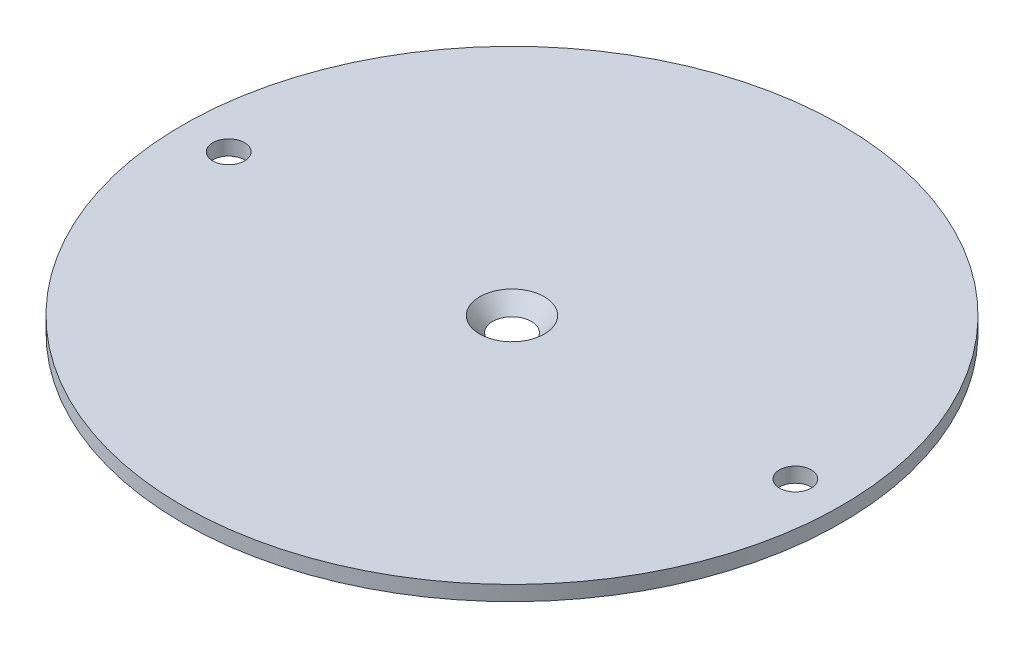
SolidWorks part; units mm, degrees
material "6061 Alloy"
ref_plane "Front Plane" through (0, 0, 0) normal (0, 0, 1) x (1, 0, 0)
ref_plane "Top Plane" through (0, 0, 0) normal (0, 1, 0) x (1, 0, 0)
ref_plane "Right Plane" through (0, 0, 0) normal (1, 0, 0) x (0, 0, -1)
sketch "Sketch2" plane through (0, 0, 0) normal (0, 1, 0) x (1, 0, 0)
  circle A0 centre (0, 0) radius 70.1675
  dimension "D1" = 140.335
extrude "Boss-Extrude1" add sketch "Sketch2" along normal blind 3.175
sketch "Sketch3" plane through (0, 3.175, 0) normal (0, 1, 0) x (1, 0, 0)
  point P0 (-60.325, 0)
  point P1 (60.325, 0)
  dimension "D1" = 60.325
  dimension "D2" = 60.325
hole_wizard "1/4 Clearance Hole1" positions "Sketch3" profile "Sketch4" hole size "1/4" standard "ANSI Inch" end condition through all
sketch "Sketch4" plane through (-60.325, 3.175, 0) normal (1, 0, 0) x (0, 0, 1)
  line L0 (0, 0) -> (0, 3.175)
  line L1 (0, 3.175) -> (3.3782, 3.175)
  line L2 (3.3782, 3.175) -> (3.3782, 0)
  line L5 (3.3782, 0) -> (0, 0)
  line L11 (0, -6.35) -> (0, 107.95) construction
  dimension "Thru Hole Dia." = 6.7564
  dimension "Thru Hole Depth" = 3.175
sketch "Sketch5" plane through (0, 3.175, 0) normal (0, 1, 0) x (1, 0, 0)
  point P0 (0, 0)
hole_wizard "CSK for 1/4 Flat Head Machine Screw1" positions "Sketch5" profile "Sketch7" countersink size "1/4" standard "ANSI Inch" end condition through all
sketch "Sketch7" plane through (0, 3.175, 0) normal (1, 0, 0) x (0, 0, 1)
  line L0 (0, 0) -> (0, 3.175)
  line L1 (0, 3.175) -> (3.3782, 3.175)
  line L2 (3.3782, 3.175) -> (3.3782, 4.0323)
  line L3 (3.3782, 4.0323) -> (6.8834, 0)
  line L5 (6.8834, 0) -> (0, 0)
  line L6 (-3.3782, 4.0323) -> (-6.8834, 0) construction
  line L11 (0, -6.35) -> (0, 107.95) construction
  dimension "Thru Hole Dia." = 6.7564
  dimension "Thru Hole Depth" = 3.175
  dimension "Near C'Sink Dia." = 13.7668
  dimension "Near C'Sink Angle" = 82
equation "\"outerdiameter\"= 5.525"
equation "\"platethickness\"= 1 / 8"
equation "\"holespacing\"= 2.375"
equation "\"D1@Sketch2\"=\"outerdiameter\""
equation "\"D1@Boss-Extrude1\"=\"platethickness\""
equation "\"D2@Sketch3\"=\"holespacing\""
equation "\"D1@Sketch3\"=\"holespacing\""
